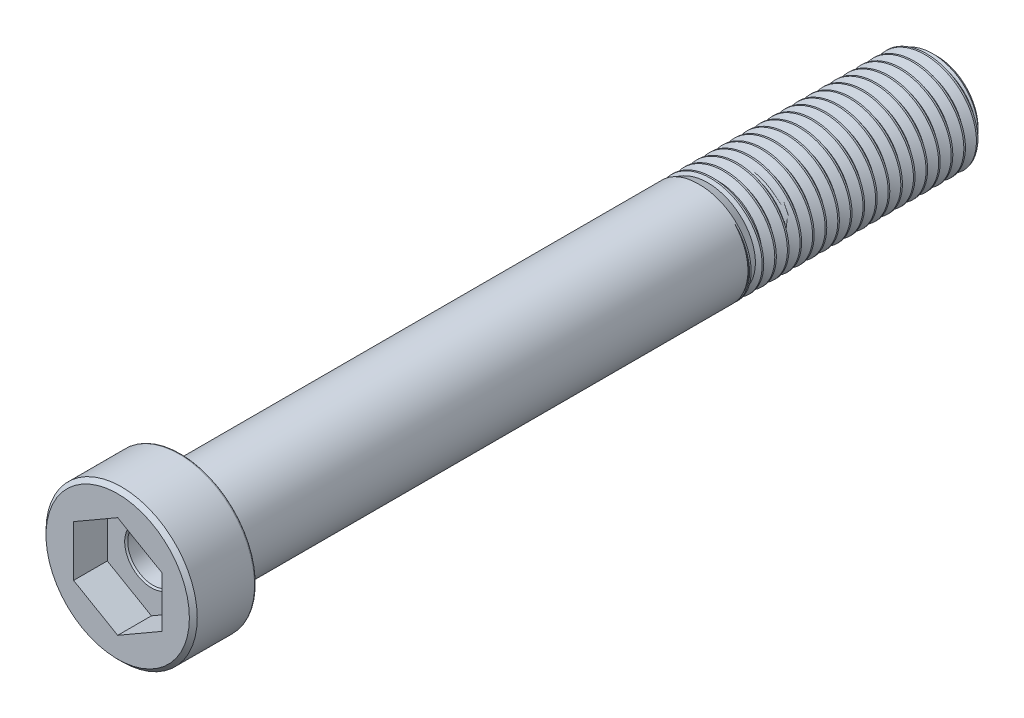
SolidWorks part; units mm, degrees
ref_plane "Front Plane" through (0, 0, 0) normal (0, 0, 1) x (1, 0, 0)
ref_plane "Top Plane" through (0, 0, 0) normal (0, 1, 0) x (1, 0, 0)
ref_plane "Right Plane" through (0, 0, 0) normal (1, 0, 0) x (0, 0, -1)
sketch "Sketch1" plane through (0, 0, 0) normal (0, 0, 1) x (1, 0, 0)
  line L1 (0, 8.0829) -> (-7, 4.0415)
  line L2 (-7, 4.0415) -> (-7, -4.0415)
  line L3 (-7, -4.0415) -> (0, -8.0829)
  line L4 (0, -8.0829) -> (7, -4.0415)
  line L5 (7, -4.0415) -> (7, 4.0415)
  line L6 (7, 4.0415) -> (0, 8.0829)
  circle A0 centre (0, 0) radius 7 construction
  point P1 (0, 7)
  dimension "Drive Size" = 14
sketch "Sketch2" plane through (0, 0, 0) normal (1, 0, 0) x (0, 0, -1)
  line L0 (-65, 0) -> (65, 0) construction
  line L1 (-65, 0) -> (-65, 12)
  line L2 (-65, 12) -> (-55, 12)
  line L3 (-55, 12) -> (-55, 0)
  line L4 (-55, 8) -> (65, 8)
  line L5 (65, 8) -> (65, 0)
  line L6 (63.5, 8) -> (65, 6.5)
  line L7 (-65, 7) -> (-59.65, 7)
  line L8 (-59.65, 7) -> (-59.65, 0)
  line L9 (-65, 4) -> (-54.3, 4)
  line L10 (-54.3, 4) -> (-54.3, 0)
  line L11 (-54.3, 0.48) -> (-56.3323, 4)
  point P2 (0, 0)
  point P10 (63, 8)
  point P12 (-59.65, 0)
  point P18 (27, 8)
  point P22 (60, 8)
  point P23 (60, -8)
  dimension "Head Height" = 10
  dimension "Length" = 120
  dimension "Thread Diameter" = 16
  dimension "Thread Pitch" = 2
  dimension "D5" = 45
  dimension "D6" = 1.5
  dimension "T" = 5.35
  dimension "Pilot Recess Diameter" = 8
  dimension "Minimum Thread Length" = 38
  dimension "Head Diameter" = 24
  dimension "D1" = 5.35
  dimension "D2" = 60
  dimension "D4" = 0.48
  dimension "D7" = 5
sketch "Sketch3" plane through (0, 0, 0) normal (1, 0, 0) x (0, 0, -1)
  line L0 (-65, 7) -> (-65, 12)
  line L1 (-65, 12) -> (-55, 12)
  line L2 (-55, 12) -> (-55, 8)
  line L3 (-55, 8) -> (63.5, 8)
  line L4 (63.5, 8) -> (65, 6.5)
  line L5 (65, 6.5) -> (65, 0)
  line L6 (65, 0) -> (-54.3, 0)
  line L8 (-56.3323, 4) -> (-59.65, 4)
  line L11 (-59.65, 7) -> (-65, 7)
  line L12 (-65, 4) -> (-54.3, 4) construction
  line L13 (-59.65, 7) -> (-59.65, 4)
  line L14 (-54.3, 0.48) -> (-56.3323, 4) construction
  line L15 (-54.3, 0.48) -> (-56.3323, 4)
  line L16 (-54.3, 0.48) -> (-54.3, 0)
revolve "Revolve1" add sketch "Sketch3" angle 360 about L6
sketch "Sketch4" plane through (0, 0, 65) normal (0, 0, 1) x (1, 0, 0)
  line L0 (0, -8.0829) -> (7, -4.0415) construction
  line L1 (-7, -4.0415) -> (0, -8.0829) construction
  line L2 (-7, 4.0415) -> (-7, -4.0415) construction
  line L3 (0, 8.0829) -> (-7, 4.0415) construction
  line L4 (7, 4.0415) -> (0, 8.0829) construction
  line L5 (7, -4.0415) -> (7, 4.0415) construction
  line L6 (0, -8.0829) -> (7, -4.0415)
  line L7 (-7, -4.0415) -> (0, -8.0829)
  line L8 (-7, 4.0415) -> (-7, -4.0415)
  line L9 (0, 8.0829) -> (-7, 4.0415)
  line L10 (7, 4.0415) -> (0, 8.0829)
  line L11 (7, -4.0415) -> (7, 4.0415)
extrude "Cut-Extrude1" cut sketch "Sketch4" against normal up to vertex (5.35 mm away) up to point (0, 7, 59.65)
chamfer "Chamfer1" distance 0.625 angle 45 1 edges at (-12, 0, 65)
chamfer "Chamfer2" distance 0.24 angle 45 1 edges at (-4, 0, 59.65)
fillet "Fillet1" radius 0.8 1 edges at (-8, 0, 55)
fillet "Fillet2" radius 0.3 1 edges at (-12, 0, 55)
ref_plane "Plane1" through (0, 0, -27) normal (0, 0, 1) x (1, 0, 0)
split "Split1" trim tools "Plane1" bodies to split 105 resulting bodies 106 107
sketch "Sketch5" plane through (0, 0, -65) normal (0, 0, -1) x (-1, 0, 0)
  circle A0 centre (0, 0) radius 8
curve "Helix/Spiral1" pitch 2 height 40 radius 8 centre (0, 0, -65) axis (0, 0, 1) start towards (0, 1, 0)
sketch "Sketch6" plane through (0, 0, 0) normal (1, 0, 0) x (0, 0, -1)
  line L0 (64.875, 8.2165) -> (65.875, 6.4845) construction
  line L1 (65.875, 6.4845) -> (66.875, 8.2165) construction
  line L2 (66.875, 8.2165) -> (64.875, 8.2165) construction
  line L3 (64.9375, 8.1083) -> (66.8125, 8.1083)
  line L4 (66.8125, 8.1083) -> (66, 6.701)
  line L5 (66, 6.701) -> (65.75, 6.701)
  line L6 (65.75, 6.701) -> (64.9375, 8.1083)
  line L7 (65.875, 6.701) -> (65.875, 6.4845) construction
  line L8 (65, 8) -> (66.75, 8) construction
  line L9 (65.875, 8.2165) -> (65.875, 8) construction
  point P12 (65.875, 8.1083)
  dimension "D1" = 2
  dimension "D2" = 0.25
sweep "Cut-Sweep1" cut profiles "Sketch6" path "Helix/Spiral1" align with end faces yes
sketch "Sketch7" plane through (0, 0, -27) normal (0, 0, 1) x (1, 0, 0)
  circle A1 centre (0, 0) radius 8
  circle A2 centre (0, 0) radius 8
  dimension "D1" = 0
extrude "Boss-Extrude1" add sketch "Sketch7" against normal up to vertex draft 20 up to point (0, 8, -65)
equation "\"D6@Sketch2\" = 0.75 * \"Thread Pitch@Sketch2\""
equation "\"D1@Sketch2\" = \"T@Sketch2\""
equation "\"D4@Sketch2\"=\"Pilot Recess Diameter@Sketch2\"*0.06"
equation "\"D1@Chamfer1\"=\"Head Height@Sketch2\"/16"
equation "\"D1@Chamfer2\"=\"Pilot Recess Diameter@Sketch2\"*0.03"
equation "\"D1@Fillet1\"=\"Thread Diameter@Sketch2\"*.05"
equation "\"D1@Fillet2\"=\"Head Height@Sketch2\"*.03"
equation "\"D4@Helix/Spiral1\"=\"Thread Pitch@Sketch2\""
equation "\"D3@Helix/Spiral1\"=\"Minimum Thread Length@Sketch2\"+\"Thread Pitch@Sketch2\""
equation "\"D2@Sketch6\"=\"D1@Sketch6\"/8"
equation "\"D1@Sketch6\"=\"Thread Pitch@Sketch2\""
equation "\"D7@Sketch2\"=\"Thread Pitch@Sketch2\"*2.5"
